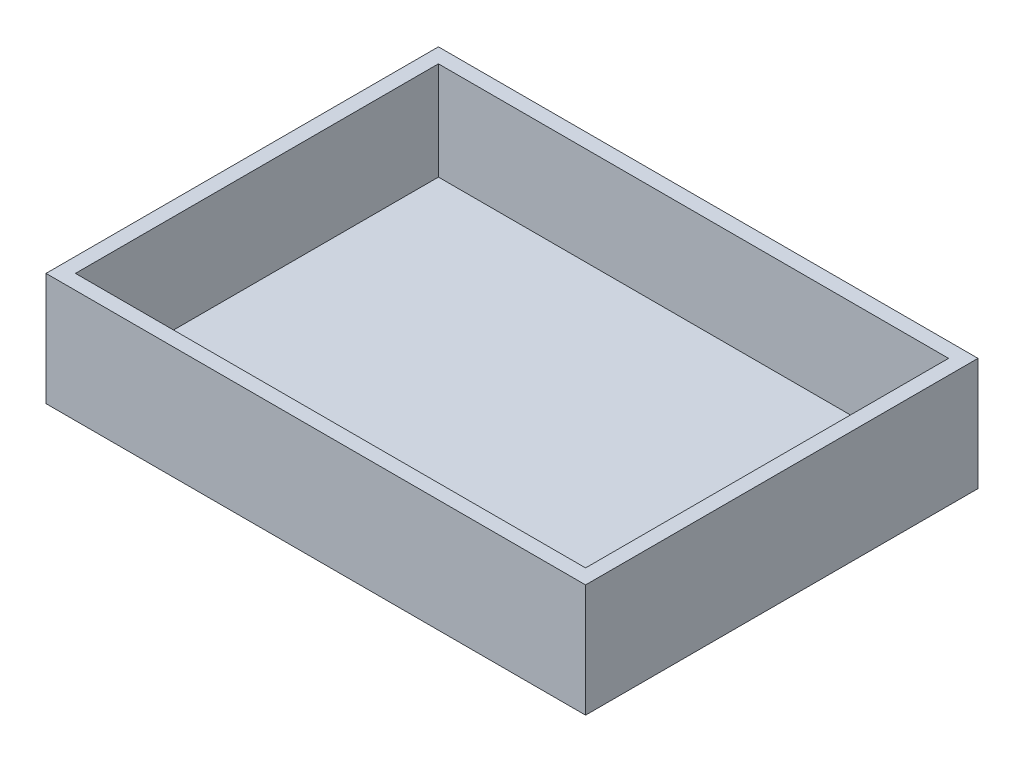
SolidWorks part; units mm, degrees
ref_plane "前视基准面" through (0, 0, 0) normal (0, 0, 1) x (1, 0, 0)
ref_plane "上视基准面" through (0, 0, 0) normal (0, 1, 0) x (1, 0, 0)
ref_plane "右视基准面" through (0, 0, 0) normal (1, 0, 0) x (0, 0, -1)
other "Configuration Table"
sketch "草图1" plane through (0, 0, 0) normal (0, 1, 0) x (1, 0, 0)
  line L1 (-27.5, 20) -> (27.5, 20)
  line L2 (-27.5, 20) -> (-27.5, -20)
  line L3 (-27.5, -20) -> (27.5, -20)
  line L4 (27.5, 20) -> (27.5, -20)
  line L5 (-27.5, 20) -> (27.5, -20) construction
  line L6 (-27.5, -20) -> (27.5, 20) construction
  point P0 (0, 0)
  dimension "D1" = 55
  dimension "D2" = 40
extrude "凸台-拉伸1" add sketch "草图1" along normal blind 11.5
shell "抽壳1" thickness 1.5 removed face at (0, 11.5, 0)
